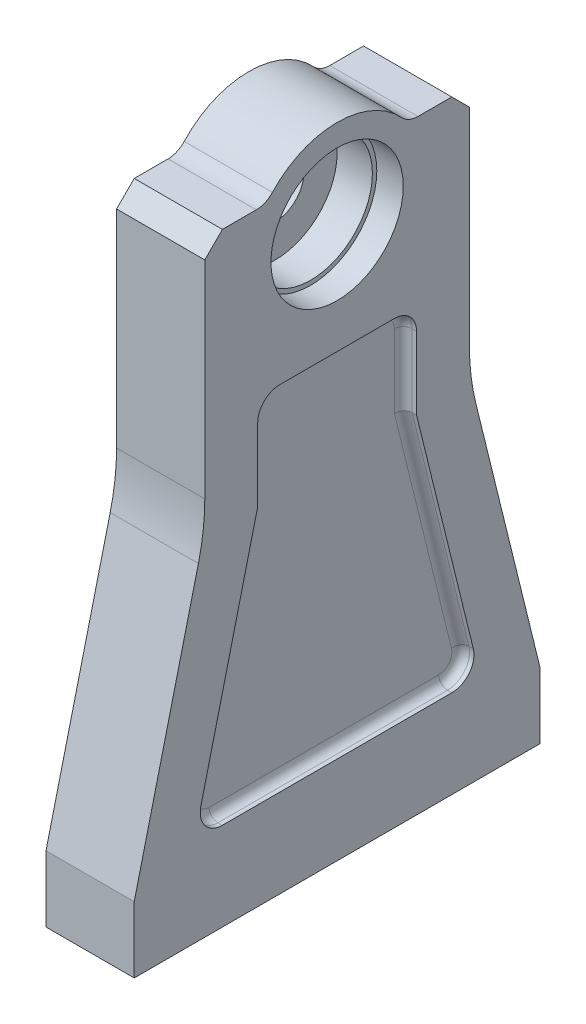
SolidWorks part; units mm, degrees
ref_plane "Front Plane" through (0, 0, 0) normal (0, 0, 1) x (1, 0, 0)
ref_plane "Top Plane" through (0, 0, 0) normal (0, 1, 0) x (1, 0, 0)
ref_plane "Right Plane" through (0, 0, 0) normal (1, 0, 0) x (0, 0, -1)
sketch "Sketch1" plane through (0, 0, 0) normal (1, 0, 0) x (0, 0, -1)
  line L1 (-16, 137) -> (-26, 137)
  line L2 (-30, 133) -> (-30, 86.0633)
  line L3 (-31.4493, 74.1124) -> (-46, 15)
  line L4 (-46, 15) -> (-46, 0)
  line L5 (-46, 0) -> (46, 0)
  line L6 (-26, 137) -> (-30, 133)
  line L7 (0, 0) -> (0, 88.4864) construction
  line L8 (46, 15) -> (46, 0)
  line L9 (31.4493, 74.1124) -> (46, 15)
  line L10 (30, 133) -> (30, 86.0633)
  line L11 (26, 137) -> (30, 133)
  line L12 (16, 137) -> (26, 137)
  arc A0 (16, 137) -> (-16, 137) centre (0, 125) ccw
  arc A1 (-30, 86.0633) -> (-31.4493, 74.1124) centre (-80, 86.0633) cw
  arc A2 (30, 86.0633) -> (31.4493, 74.1124) centre (80, 86.0633) ccw
  point P5 (-30, 137)
  point P13 (-30, 80)
  point P23 (0, 0)
  dimension "D1" = 40
  dimension "D8" = 50
  dimension "D2" = 12
  dimension "D3" = 125
  dimension "D4" = 65
  dimension "D5" = 15
  dimension "D6" = 4
  dimension "D7" = 45
  dimension "D9" = 46
  dimension "D10" = 30
extrude "Boss-Extrude1" add sketch "Sketch1" along normal mid plane 20
sketch "Sketch2" plane through (10, 0, 0) normal (1, 0, 0) x (0, 0, -1)
  line L0 (13, 100) -> (-13, 100)
  line L1 (-18, 95) -> (-18, 78.5448)
  line L2 (0, 0) -> (0, 100) construction
  line L3 (18, 78.5448) -> (30.8861, 26.1951)
  line L4 (-26.031, 20) -> (26.031, 20)
  line L5 (-30, 133) -> (-30, 86.0633) construction
  line L6 (18, 95) -> (18, 78.5448)
  line L7 (-46, 0) -> (46, 0) construction
  line L10 (-19.7971, 71.2442) -> (-34.3478, 12.1318)
  line L11 (-18, 78.5448) -> (-30.8861, 26.1951)
  arc A0 (-30.8861, 26.1951) -> (-26.031, 20) centre (-26.031, 25) ccw
  arc A1 (-13, 100) -> (-18, 95) centre (-13, 95) ccw
  arc A2 (30.8861, 26.1951) -> (26.031, 20) centre (26.031, 25) cw
  arc A3 (13, 100) -> (18, 95) centre (13, 95) cw
  point P15 (-18, 100)
  point P18 (0, 20)
  dimension "D6" = 5
  dimension "D1" = 12
  dimension "D2" = 20
  dimension "D3" = 12
  dimension "D4" = 18
  dimension "D5" = 100
extrude "Cut-Extrude1" cut sketch "Sketch2" against normal blind 3
fillet "Fillet1" radius 2 10 edges at (7, 86.7724, 18) (7, 98.5355, 16.5355) (7, 100, 0) (7, 98.5355, -16.5355) (7, 86.7724, -18) (7, 52.3699, -24.443) (7, 21.9158, -29.9665) (7, 20, 0) (7, 21.9158, 29.9665) (7, 52.3699, 24.443)
mirror "Mirror1" about plane through (0, 0, 0) normal (1, 0, 0) of "Cut-Extrude1", "Fillet1"
sketch "Sketch3" plane through (10, 0, 0) normal (1, 0, 0) x (0, 0, -1)
  circle A0 centre (0, 125) radius 15
  circle A1 centre (0, 125) radius 14
  circle A2 centre (0, 125) radius 6.5
  dimension "D1" = 30
  dimension "D2" = 28
  dimension "D3" = 13
extrude "Cut-Extrude2" cut sketch "Sketch3" against normal blind 6 contours A0 A1 region at (10, 125, 14.5757)
extrude "Cut-Extrude3" cut sketch "Sketch3<3>" against normal blind 14 contours A1
sketch "Sketch3<3>" plane through (10, 0, 0) normal (1, 0, 0) x (0, 0, -1) same geometry as "Sketch3"
extrude "Cut-Extrude4" cut sketch "Sketch3<4>" against normal through all contours A2 region at (10, 125, 0)
sketch "Sketch3<4>" plane through (10, 0, 0) normal (1, 0, 0) x (0, 0, -1) same geometry as "Sketch3"
sketch "Sketch4" plane through (0, 0, 0) normal (0, -1, 0) x (1, 0, 0)
  circle A0 centre (0, 30) radius 5
  circle A1 centre (0, -30) radius 5
  point P4 (0, 0)
  dimension "D1" = 10
  dimension "D2" = 30
  dimension "D3" = 60
extrude "Cut-Extrude5" cut sketch "Sketch4" against normal blind 20
fillet "Fillet2" radius 5 2 edges at (0, 137, -16) (0, 137, 16)
